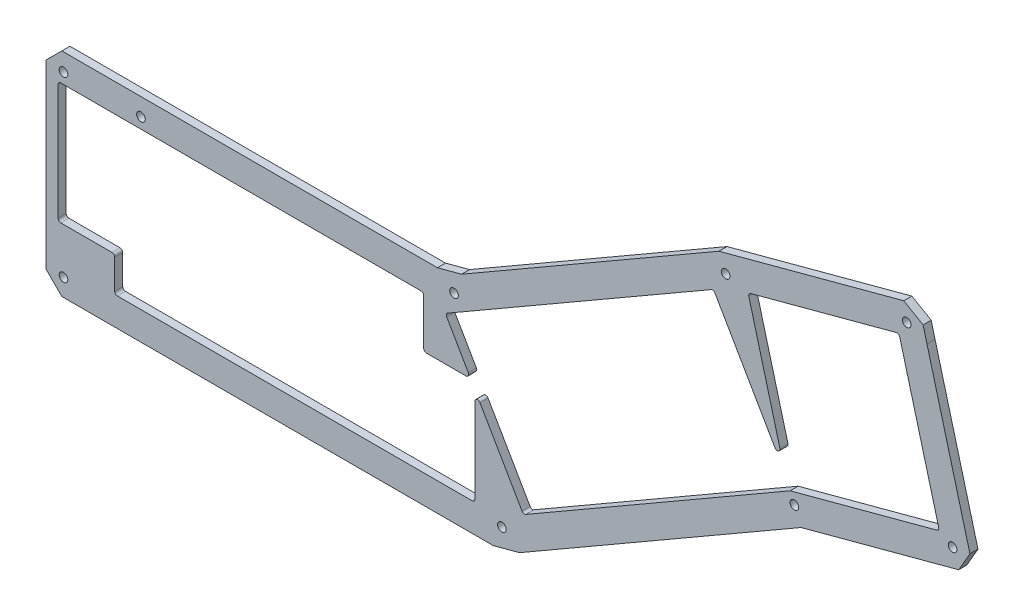
SolidWorks part; units mm, degrees
ref_plane "Plan de face" through (0, 0, 0) normal (0, 0, 1) x (1, 0, 0)
ref_plane "Plan de dessus" through (0, 0, 0) normal (0, 1, 0) x (1, 0, 0)
ref_plane "Plan de droite" through (0, 0, 0) normal (1, 0, 0) x (0, 0, -1)
sketch "Esquisse1" plane through (0, 0, 0) normal (0, 0, 1) x (1, 0, 0)
  line L0 (-73.9886, 18.0851) -> (-59.9886, 18.0851) construction
  line L1 (-73.9886, 37.0851) -> (-59.9886, 37.0851) construction
  line L2 (-73.9886, 37.0851) -> (-73.9886, 23.0851) construction
  line L3 (-73.9886, 23.0851) -> (-59.9886, 23.0851) construction
  line L4 (-59.9886, 37.0851) -> (-59.9886, 23.0851) construction
  line L5 (-73.9886, 18.0851) -> (-73.9886, 4.0851) construction
  line L6 (-73.9886, 4.0851) -> (-59.9886, 4.0851) construction
  line L7 (-59.9886, 18.0851) -> (-59.9886, 4.0851) construction
  line L8 (-73.9886, -0.9149) -> (-59.9886, -0.9149) construction
  line L9 (-73.9886, -0.9149) -> (-73.9886, -14.9149) construction
  line L10 (-73.9886, -14.9149) -> (-59.9886, -14.9149) construction
  line L11 (-59.9886, -0.9149) -> (-59.9886, -14.9149) construction
  line L12 (-73.9886, 37.0851) -> (-73.9886, 18.0851) construction
  line L13 (-54.9886, 18.0851) -> (-40.9886, 18.0851) construction
  line L14 (-54.9886, 37.0851) -> (-40.9886, 37.0851) construction
  line L15 (-54.9886, 37.0851) -> (-54.9886, 23.0851) construction
  line L16 (-54.9886, 23.0851) -> (-40.9886, 23.0851) construction
  line L17 (-40.9886, 37.0851) -> (-40.9886, 23.0851) construction
  line L18 (-54.9886, 18.0851) -> (-54.9886, 4.0851) construction
  line L19 (-54.9886, 4.0851) -> (-40.9886, 4.0851) construction
  line L20 (-40.9886, 18.0851) -> (-40.9886, 4.0851) construction
  line L21 (-54.9886, -0.9149) -> (-40.9886, -0.9149) construction
  line L22 (-54.9886, -0.9149) -> (-54.9886, -14.9149) construction
  line L23 (-54.9886, -14.9149) -> (-40.9886, -14.9149) construction
  line L24 (-40.9886, -0.9149) -> (-40.9886, -14.9149) construction
  line L25 (-54.9886, 37.0851) -> (-54.9886, 18.0851) construction
  line L26 (-35.9886, 18.0851) -> (-21.9886, 18.0851) construction
  line L27 (-35.9886, 37.0851) -> (-21.9886, 37.0851) construction
  line L28 (-35.9886, 37.0851) -> (-35.9886, 23.0851) construction
  line L29 (-35.9886, 23.0851) -> (-21.9886, 23.0851) construction
  line L30 (-21.9886, 37.0851) -> (-21.9886, 23.0851) construction
  line L31 (-35.9886, 18.0851) -> (-35.9886, 4.0851) construction
  line L32 (-35.9886, 4.0851) -> (-21.9886, 4.0851) construction
  line L33 (-21.9886, 18.0851) -> (-21.9886, 4.0851) construction
  line L34 (-35.9886, -0.9149) -> (-21.9886, -0.9149) construction
  line L35 (-35.9886, -0.9149) -> (-35.9886, -14.9149) construction
  line L36 (-35.9886, -14.9149) -> (-21.9886, -14.9149) construction
  line L37 (-21.9886, -0.9149) -> (-21.9886, -14.9149) construction
  line L38 (-35.9886, 37.0851) -> (-35.9886, 18.0851) construction
  line L39 (-16.9886, 18.0851) -> (-2.9886, 18.0851) construction
  line L40 (-16.9886, 37.0851) -> (-2.9886, 37.0851) construction
  line L41 (-16.9886, 37.0851) -> (-16.9886, 23.0851) construction
  line L42 (-16.9886, 23.0851) -> (-2.9886, 23.0851) construction
  line L43 (-2.9886, 37.0851) -> (-2.9886, 23.0851) construction
  line L44 (-16.9886, 18.0851) -> (-16.9886, 4.0851) construction
  line L45 (-16.9886, 4.0851) -> (-2.9886, 4.0851) construction
  line L46 (-2.9886, 18.0851) -> (-2.9886, 4.0851) construction
  line L47 (-16.9886, -0.9149) -> (-2.9886, -0.9149) construction
  line L48 (-16.9886, -0.9149) -> (-16.9886, -14.9149) construction
  line L49 (-16.9886, -14.9149) -> (-2.9886, -14.9149) construction
  line L50 (-2.9886, -0.9149) -> (-2.9886, -14.9149) construction
  line L51 (-16.9886, 37.0851) -> (-16.9886, 18.0851) construction
  line L52 (2.0114, 18.0851) -> (16.0114, 18.0851) construction
  line L53 (2.0114, 37.0851) -> (16.0114, 37.0851) construction
  line L54 (2.0114, 37.0851) -> (2.0114, 23.0851) construction
  line L55 (2.0114, 23.0851) -> (16.0114, 23.0851) construction
  line L56 (16.0114, 37.0851) -> (16.0114, 23.0851) construction
  line L57 (2.0114, 18.0851) -> (2.0114, 4.0851) construction
  line L58 (2.0114, 4.0851) -> (16.0114, 4.0851) construction
  line L59 (16.0114, 18.0851) -> (16.0114, 4.0851) construction
  line L60 (2.0114, -0.9149) -> (16.0114, -0.9149) construction
  line L61 (2.0114, -0.9149) -> (2.0114, -14.9149) construction
  line L62 (2.0114, -14.9149) -> (16.0114, -14.9149) construction
  line L63 (16.0114, -0.9149) -> (16.0114, -14.9149) construction
  line L64 (2.0114, 37.0851) -> (2.0114, 18.0851) construction
  line L65 (21.0114, 18.0851) -> (35.0114, 18.0851) construction
  line L66 (21.0114, 37.0851) -> (35.0114, 37.0851) construction
  line L67 (21.0114, 37.0851) -> (21.0114, 23.0851) construction
  line L68 (21.0114, 23.0851) -> (35.0114, 23.0851) construction
  line L69 (35.0114, 37.0851) -> (35.0114, 23.0851) construction
  line L70 (21.0114, 18.0851) -> (21.0114, 4.0851) construction
  line L71 (21.0114, 4.0851) -> (35.0114, 4.0851) construction
  line L72 (35.0114, 18.0851) -> (35.0114, 4.0851) construction
  line L73 (21.0114, -0.9149) -> (35.0114, -0.9149) construction
  line L74 (21.0114, -0.9149) -> (21.0114, -14.9149) construction
  line L75 (21.0114, -14.9149) -> (35.0114, -14.9149) construction
  line L76 (35.0114, -0.9149) -> (35.0114, -14.9149) construction
  line L77 (21.0114, 37.0851) -> (21.0114, 18.0851) construction
  line L78 (40.0114, 18.0851) -> (54.0114, 18.0851) construction
  line L79 (-97.7538, 39.0851) -> (-97.7538, 2.0851)
  line L80 (-97.7538, 39.0851) -> (-97.7538, 1.0851) construction
  line L81 (-76.7538, 0.0851) -> (-76.7538, -16.9149) construction
  line L82 (-95.7538, 44.0851) -> (-53.0442, 44.0851) construction
  line L83 (40.0114, 18.0851) -> (40.0114, 4.0851) construction
  line L84 (40.0114, 4.0851) -> (54.0114, 4.0851) construction
  line L85 (54.0114, 18.0851) -> (54.0114, 4.0851) construction
  line L86 (40.0114, -0.9149) -> (54.0114, -0.9149) construction
  line L87 (40.0114, -0.9149) -> (40.0114, -14.9149) construction
  line L88 (40.0114, -14.9149) -> (54.0114, -14.9149) construction
  line L89 (54.0114, -0.9149) -> (54.0114, -14.9149) construction
  line L90 (40.0114, 20.0851) -> (40.0114, 18.0851) construction
  line L91 (-73.9886, 18.0851) -> (-54.9886, 18.0851) construction
  line L92 (56.0114, 20.0851) -> (56.7532, 18.8002) construction
  line L93 (-66.9886, 37.0851) -> (-66.9886, 44.0851) construction
  line L94 (67.3933, 2.371) -> (74.3933, -9.7534) construction
  line L95 (146.1202, 94.012) -> (168.4398, 55.3534)
  line L96 (158.7183, 99.2303) -> (170.2717, 56.1122)
  line L97 (19.0114, 39.0851) -> (37.0114, 39.0851) construction
  line L98 (37.0114, 39.0851) -> (37.0114, 21.0851) construction
  line L99 (19.0114, 21.0851) -> (37.0114, 21.0851) construction
  line L100 (19.0114, 39.0851) -> (19.0114, 21.0851) construction
  line L101 (79.4363, 55.512) -> (88.4363, 39.9235) construction
  line L102 (88.4363, 39.9235) -> (72.8478, 30.9235) construction
  line L103 (63.8478, 46.512) -> (72.8478, 30.9235) construction
  line L104 (79.4363, 55.512) -> (63.8478, 46.512) construction
  line L105 (62.9818, 46.012) -> (71.9818, 30.4235) construction
  line L106 (71.9818, 30.4235) -> (56.3933, 21.4235) construction
  line L107 (47.3933, 37.012) -> (56.3933, 21.4235) construction
  line L108 (62.9818, 46.012) -> (47.3933, 37.012) construction
  line L109 (164.2542, 60.603) -> (148.6657, 51.603) construction
  line L110 (62.2497, 43.2799) -> (71.7497, 26.8254) construction
  line L111 (78.7042, 52.7799) -> (88.2042, 36.3254) construction
  line L112 (95.1587, 62.2799) -> (104.6587, 45.8254) construction
  line L113 (111.6132, 71.7799) -> (121.1132, 55.3254) construction
  line L114 (128.0677, 81.2799) -> (137.5677, 64.8254) construction
  line L115 (144.5221, 90.7799) -> (154.0221, 74.3254) construction
  line L116 (148.6657, 51.603) -> (157.6657, 36.0146) construction
  line L117 (69.1254, 3.371) -> (76.1254, -8.7534) construction
  line L118 (88.2497, -1.7534) -> (76.1254, -8.7534) construction
  line L119 (81.2497, 10.371) -> (88.2497, -1.7534) construction
  line L120 (81.2497, 10.371) -> (69.1254, 3.371) construction
  line L121 (59.6254, 19.8254) -> (66.6254, 7.7011) construction
  line L122 (78.7497, 14.7011) -> (66.6254, 7.7011) construction
  line L123 (71.7497, 26.8254) -> (78.7497, 14.7011) construction
  line L124 (50.1254, 36.2799) -> (57.1254, 24.1556) construction
  line L125 (69.2497, 31.1556) -> (57.1254, 24.1556) construction
  line L126 (62.2497, 43.2799) -> (69.2497, 31.1556) construction
  line L127 (62.2497, 43.2799) -> (50.1254, 36.2799) construction
  line L128 (71.7497, 26.8254) -> (59.6254, 19.8254) construction
  line L129 (85.5799, 12.871) -> (92.5799, 0.7466) construction
  line L130 (104.7042, 7.7466) -> (92.5799, 0.7466) construction
  line L131 (97.7042, 19.871) -> (104.7042, 7.7466) construction
  line L132 (97.7042, 19.871) -> (85.5799, 12.871) construction
  line L133 (76.0799, 29.3254) -> (83.0799, 17.2011) construction
  line L134 (95.2042, 24.2011) -> (83.0799, 17.2011) construction
  line L135 (88.2042, 36.3254) -> (95.2042, 24.2011) construction
  line L136 (66.5799, 45.7799) -> (73.5799, 33.6556) construction
  line L137 (85.7042, 40.6556) -> (73.5799, 33.6556) construction
  line L138 (78.7042, 52.7799) -> (85.7042, 40.6556) construction
  line L139 (78.7042, 52.7799) -> (66.5799, 45.7799) construction
  line L140 (88.2042, 36.3254) -> (76.0799, 29.3254) construction
  line L141 (102.0343, 22.371) -> (109.0343, 10.2466) construction
  line L142 (121.1587, 17.2466) -> (109.0343, 10.2466) construction
  line L143 (114.1587, 29.371) -> (121.1587, 17.2466) construction
  line L144 (114.1587, 29.371) -> (102.0343, 22.371) construction
  line L145 (92.5343, 38.8254) -> (99.5343, 26.7011) construction
  line L146 (111.6587, 33.7011) -> (99.5343, 26.7011) construction
  line L147 (104.6587, 45.8254) -> (111.6587, 33.7011) construction
  line L148 (83.0343, 55.2799) -> (90.0343, 43.1556) construction
  line L149 (102.1587, 50.1556) -> (90.0343, 43.1556) construction
  line L150 (95.1587, 62.2799) -> (102.1587, 50.1556) construction
  line L151 (95.1587, 62.2799) -> (83.0343, 55.2799) construction
  line L152 (104.6587, 45.8254) -> (92.5343, 38.8254) construction
  line L153 (118.4888, 31.871) -> (125.4888, 19.7466) construction
  line L154 (137.6132, 26.7466) -> (125.4888, 19.7466) construction
  line L155 (130.6132, 38.871) -> (137.6132, 26.7466) construction
  line L156 (130.6132, 38.871) -> (118.4888, 31.871) construction
  line L157 (108.9888, 48.3254) -> (115.9888, 36.2011) construction
  line L158 (128.1132, 43.2011) -> (115.9888, 36.2011) construction
  line L159 (121.1132, 55.3254) -> (128.1132, 43.2011) construction
  line L160 (99.4888, 64.7799) -> (106.4888, 52.6556) construction
  line L161 (118.6132, 59.6556) -> (106.4888, 52.6556) construction
  line L162 (111.6132, 71.7799) -> (118.6132, 59.6556) construction
  line L163 (111.6132, 71.7799) -> (99.4888, 64.7799) construction
  line L164 (121.1132, 55.3254) -> (108.9888, 48.3254) construction
  line L165 (134.9433, 41.371) -> (141.9433, 29.2466) construction
  line L166 (154.0677, 36.2466) -> (141.9433, 29.2466) construction
  line L167 (147.0677, 48.371) -> (154.0677, 36.2466) construction
  line L168 (147.0677, 48.371) -> (134.9433, 41.371) construction
  line L169 (125.4433, 57.8254) -> (132.4433, 45.7011) construction
  line L170 (144.5677, 52.7011) -> (132.4433, 45.7011) construction
  line L171 (137.5677, 64.8254) -> (144.5677, 52.7011) construction
  line L172 (115.9433, 74.2799) -> (122.9433, 62.1556) construction
  line L173 (135.0677, 69.1556) -> (122.9433, 62.1556) construction
  line L174 (128.0677, 81.2799) -> (135.0677, 69.1556) construction
  line L175 (128.0677, 81.2799) -> (115.9433, 74.2799) construction
  line L176 (137.5677, 64.8254) -> (125.4433, 57.8254) construction
  line L177 (151.3978, 50.871) -> (158.3978, 38.7466) construction
  line L178 (170.5221, 45.7466) -> (158.3978, 38.7466) construction
  line L179 (163.5221, 57.871) -> (170.5221, 45.7466) construction
  line L180 (163.5221, 57.871) -> (151.3978, 50.871) construction
  line L181 (141.8978, 67.3254) -> (148.8978, 55.2011) construction
  line L182 (161.0221, 62.2011) -> (148.8978, 55.2011) construction
  line L183 (154.0221, 74.3254) -> (161.0221, 62.2011) construction
  line L184 (132.3978, 83.7799) -> (139.3978, 71.6556) construction
  line L185 (151.5221, 78.6556) -> (139.3978, 71.6556) construction
  line L186 (144.5221, 90.7799) -> (151.5221, 78.6556) construction
  line L187 (144.5221, 90.7799) -> (132.3978, 83.7799) construction
  line L188 (154.0221, 74.3254) -> (141.8978, 67.3254) construction
  line L189 (173.2542, 45.0146) -> (157.6657, 36.0146) construction
  line L190 (164.2542, 60.603) -> (173.2542, 45.0146) construction
  line L191 (178.3169, 34.0986) -> (169.0534, 56.4627) construction
  line L192 (169.5193, 62.7839) -> (174.1781, 45.3972) construction
  line L193 (174.1781, 45.3972) -> (191.5647, 50.056) construction
  line L194 (186.906, 67.4426) -> (191.5647, 50.056) construction
  line L195 (162.1337, 98.0749) -> (167.0513, 79.7223) construction
  line L196 (169.5193, 62.7839) -> (186.906, 67.4426) construction
  line L197 (167.0513, 79.7223) -> (180.5742, 83.3457) construction
  line L198 (162.1337, 98.0749) -> (175.6567, 101.6983) construction
  line L199 (162.1337, 98.0749) -> (165.7572, 84.5519) construction
  line L200 (165.7572, 84.5519) -> (179.2801, 88.1754) construction
  line L201 (175.6567, 101.6983) -> (179.2801, 88.1754) construction
  line L202 (167.0513, 79.7223) -> (170.6747, 66.1993) construction
  line L203 (170.6747, 66.1993) -> (184.1977, 69.8228) construction
  line L204 (180.5742, 83.3457) -> (184.1977, 69.8228) construction
  line L205 (171.9688, 61.3697) -> (185.4918, 64.9932) construction
  line L206 (171.9688, 61.3697) -> (175.5923, 47.8467) construction
  line L207 (175.5923, 47.8467) -> (189.1152, 51.4702) construction
  line L208 (185.4918, 64.9932) -> (189.1152, 51.4702) construction
  line L209 (185.4038, 84.6398) -> (198.9268, 88.2633) construction
  line L210 (180.4863, 102.9924) -> (194.0092, 106.6159) construction
  line L211 (180.4863, 102.9924) -> (184.1097, 89.4695) construction
  line L212 (184.1097, 89.4695) -> (197.6327, 93.0929) construction
  line L213 (194.0092, 106.6159) -> (197.6327, 93.0929) construction
  line L214 (185.4038, 84.6398) -> (189.0273, 71.1169) construction
  line L215 (189.0273, 71.1169) -> (202.5503, 74.7403) construction
  line L216 (198.9268, 88.2633) -> (202.5503, 74.7403) construction
  line L217 (190.3214, 66.2873) -> (203.8444, 69.9107) construction
  line L218 (190.3214, 66.2873) -> (193.9449, 52.7643) construction
  line L219 (193.9449, 52.7643) -> (207.4678, 56.3878) construction
  line L220 (203.8444, 69.9107) -> (207.4678, 56.3878) construction
  line L221 (187.8719, 67.7015) -> (192.5307, 50.3148) construction
  line L222 (192.5307, 50.3148) -> (209.9173, 54.9735) construction
  line L223 (205.2586, 72.3602) -> (209.9173, 54.9735) construction
  line L224 (180.4863, 102.9924) -> (185.4038, 84.6398) construction
  line L225 (187.8719, 67.7015) -> (205.2586, 72.3602) construction
  line L226 (203.7564, 89.5574) -> (217.2794, 93.1809) construction
  line L227 (198.8389, 107.91) -> (212.3618, 111.5335) construction
  line L228 (198.8389, 107.91) -> (202.4623, 94.387) construction
  line L229 (202.4623, 94.387) -> (215.9853, 98.0105) construction
  line L230 (212.3618, 111.5335) -> (215.9853, 98.0105) construction
  line L231 (203.7564, 89.5574) -> (207.3799, 76.0344) construction
  line L232 (207.3799, 76.0344) -> (220.9029, 79.6579) construction
  line L233 (217.2794, 93.1809) -> (220.9029, 79.6579) construction
  line L234 (208.674, 71.2048) -> (222.197, 74.8283) construction
  line L235 (208.674, 71.2048) -> (212.2975, 57.6819) construction
  line L236 (212.2975, 57.6819) -> (225.8204, 61.3053) construction
  line L237 (222.197, 74.8283) -> (225.8204, 61.3053) construction
  line L238 (206.2245, 72.619) -> (210.8833, 55.2324) construction
  line L239 (210.8833, 55.2324) -> (228.2699, 59.8911) construction
  line L240 (223.6112, 77.2778) -> (228.2699, 59.8911) construction
  line L241 (198.8389, 107.91) -> (203.7564, 89.5574) construction
  line L242 (206.2245, 72.619) -> (223.6112, 77.2778) construction
  line L243 (167.0513, 79.7223) -> (185.4038, 84.6398) construction
  line L244 (38.0114, 20.0851) -> (56.0114, 20.0851) construction
  line L245 (56.0114, 20.0851) -> (56.0114, 2.0851) construction
  line L246 (38.0114, 2.0851) -> (56.0114, 2.0851) construction
  line L247 (38.0114, 20.0851) -> (38.0114, 2.0851) construction
  line L248 (72.4818, 29.5575) -> (56.8933, 20.5575) construction
  line L249 (56.8933, 20.5575) -> (65.8933, 4.969) construction
  line L250 (81.4818, 13.969) -> (65.8933, 4.969) construction
  line L251 (72.4818, 29.5575) -> (81.4818, 13.969) construction
  line L252 (56.8933, 20.5575) -> (57.6111, 19.3142) construction
  line L253 (164.6018, 81.1365) -> (169.2605, 63.7498) construction
  line L254 (169.2605, 63.7498) -> (186.6472, 68.4086) construction
  line L255 (181.9884, 85.7952) -> (186.6472, 68.4086) construction
  line L256 (164.6018, 81.1365) -> (181.9884, 85.7952) construction
  line L257 (154.7542, 77.0575) -> (163.7542, 61.469) construction
  line L258 (163.7542, 61.469) -> (148.1657, 52.469) construction
  line L259 (139.1657, 68.0575) -> (148.1657, 52.469) construction
  line L260 (154.7542, 77.0575) -> (139.1657, 68.0575) construction
  line L261 (196.3894, 109.3242) -> (213.776, 113.983) construction
  line L262 (-94.7538, 35.7952) -> (-76.7538, 35.7952) construction
  line L263 (-94.7538, 35.7952) -> (-94.7538, 2.7952) construction
  line L264 (-94.7538, 2.7952) -> (-76.7538, 2.7952) construction
  line L265 (-76.7538, 35.7952) -> (-76.7538, 2.7952) construction
  line L266 (213.776, 113.983) -> (218.4348, 96.5963) construction
  line L267 (201.0481, 91.9375) -> (218.4348, 96.5963) construction
  line L268 (196.3894, 109.3242) -> (201.0481, 91.9375) construction
  line L269 (-75.9886, -16.9149) -> (-57.9886, -16.9149) construction
  line L270 (-57.9886, 1.0851) -> (-57.9886, -16.9149) construction
  line L271 (-75.9886, 1.0851) -> (-57.9886, 1.0851) construction
  line L272 (-75.9886, 1.0851) -> (-75.9886, -16.9149) construction
  line L273 (38.0114, -16.9149) -> (56.0114, -16.9149) construction
  line L274 (56.0114, 1.0851) -> (56.0114, -16.9149) construction
  line L275 (38.0114, 1.0851) -> (56.0114, 1.0851) construction
  line L276 (38.0114, 1.0851) -> (38.0114, -16.9149) construction
  line L277 (-75.9886, 39.0851) -> (-57.9886, 39.0851) construction
  line L278 (-57.9886, 39.0851) -> (-57.9886, 21.0851) construction
  line L279 (-75.9886, 21.0851) -> (-57.9886, 21.0851) construction
  line L280 (-75.9886, 39.0851) -> (-75.9886, 21.0851) construction
  line L281 (145.2542, 93.512) -> (129.6657, 84.512) construction
  line L282 (129.6657, 84.512) -> (138.6657, 68.9235) construction
  line L283 (154.2542, 77.9235) -> (138.6657, 68.9235) construction
  line L284 (145.2542, 93.512) -> (154.2542, 77.9235) construction
  line L285 (223.4353, 116.5711) -> (228.0941, 99.1845) construction
  line L286 (148.2159, 106.7689) -> (211.1879, 123.6422) construction
  line L287 (177.5508, 35.9482) -> (235.6877, 51.5259) construction
  line L288 (177.5508, 35.9482) -> (72.9989, -24.4149) construction
  line L289 (-95.7538, -26.9149) -> (63.6687, -26.9149) construction
  line L290 (-100.7538, 35.7952) -> (-100.7538, -21.9149) construction
  line L291 (-75.9886, 49.0851) -> (43.3046, 49.0851) construction
  line L292 (148.2159, 106.7689) -> (52.6347, 51.5851) construction
  line L293 (-75.9886, 49.0851) -> (-57.9886, 49.0851) construction
  line L294 (140.2542, 102.1722) -> (124.6657, 93.1722) construction
  line L295 (193.8012, 118.9835) -> (211.1879, 123.6422) construction
  line L296 (213.4714, 45.5731) -> (230.8581, 50.2318) construction
  line L297 (38.0114, -26.9149) -> (38.0114, -85.4624) construction
  line L298 (178.2542, 36.3543) -> (162.6657, 27.3543) construction
  line L299 (38.0114, -26.9149) -> (56.0114, -26.9149) construction
  line L300 (-100.7538, 2.7952) -> (-100.7538, -38.0419) construction
  line L301 (-100.7538, 35.7952) -> (-100.7538, 2.7952) construction
  line L302 (-75.9886, 49.0851) -> (-95.7538, 49.0851) construction
  line L303 (-100.7538, 44.0851) -> (-100.7538, 35.7952) construction
  line L304 (211.1879, 123.6422) -> (216.0732, 124.9512) construction
  line L305 (222.1691, 121.4083) -> (223.4353, 116.5711) construction
  line L306 (228.0941, 99.1845) -> (239.2233, 57.6497) construction
  line L307 (216.0732, 124.9512) -> (222.1691, 121.4083) construction
  line L308 (235.6877, 51.5259) -> (239.2233, 57.6497) construction
  line L309 (63.6687, -26.9149) -> (72.9989, -24.4149) construction
  line L310 (52.6347, 51.5851) -> (43.3046, 49.0851) construction
  line L311 (-95.7538, 49.0851) -> (-100.7538, 44.0851) construction
  line L312 (-100.7538, -21.9149) -> (-95.7538, -26.9149) construction
  line L313 (-95.7538, 49.0851) -> (-95.7538, 44.0851) construction
  line L314 (-95.7538, 44.0851) -> (-100.7538, 44.0851) construction
  line L315 (-95.7538, -26.9149) -> (-95.7538, -21.9149) construction
  line L316 (68.3338, -25.6649) -> (67.0397, -20.8353) construction
  line L317 (47.9697, 50.3351) -> (49.2637, 45.5055) construction
  line L318 (177.5508, 35.9482) -> (175.6374, 40.5676) construction
  line L319 (148.2159, 106.7689) -> (150.1293, 102.1495) construction
  line L320 (239.2233, 57.6497) -> (234.3936, 56.3556) construction
  line L321 (216.0732, 124.9512) -> (217.3634, 120.1206) construction
  line L322 (146.1202, 94.012) -> (155.1202, 78.4235) construction
  line L323 (-76.7538, 35.7952) -> (-96.7538, 35.7952) construction
  line L324 (148.6019, 105.8371) -> (53.0207, 50.6533) construction
  line L325 (163.6358, 80.8777) -> (168.2946, 63.491) construction
  line L326 (57.0114, 14.621) -> (57.0114, -16.9149)
  line L327 (-77.7538, 1.0851) -> (-96.7538, 1.0851) construction
  line L328 (-96.7538, 39.0851) -> (-96.7538, 1.0851) construction
  line L329 (53.0207, 50.6533) -> (43.4362, 48.0851) construction
  line L330 (-75.9886, 48.0851) -> (43.4362, 48.0851) construction
  line L331 (-75.9886, 48.0851) -> (-95.3395, 48.0851) construction
  line L332 (-95.3395, 48.0851) -> (-99.7538, 43.6709) construction
  line L333 (-99.7538, 43.6709) -> (-99.7538, 35.7952) construction
  line L334 (-99.7538, 35.7952) -> (-99.7538, -21.5007) construction
  line L335 (-99.7538, -21.5007) -> (-95.3395, -25.9149) construction
  line L336 (-95.3395, -25.9149) -> (63.5371, -25.9149) construction
  line L337 (63.5371, -25.9149) -> (72.6129, -23.483) construction
  line L338 (177.1648, 36.88) -> (72.6129, -23.483) construction
  line L339 (177.1648, 36.88) -> (235.0288, 52.3847) construction
  line L340 (235.0288, 52.3847) -> (238.1501, 57.7909) construction
  line L341 (227.1281, 98.9257) -> (238.1501, 57.7909) construction
  line L342 (222.4686, 116.3151) -> (227.1281, 98.9257) construction
  line L343 (221.307, 120.7527) -> (222.4686, 116.3151) construction
  line L344 (215.9303, 123.8777) -> (221.307, 120.7527) construction
  line L345 (211.4467, 122.6763) -> (215.9303, 123.8777) construction
  line L346 (148.6019, 105.8371) -> (211.4467, 122.6763) construction
  line L347 (214.742, 114.2418) -> (229.2358, 60.1499)
  line L348 (174.0769, 44.3349) -> (228.5287, 58.9252)
  line L349 (174.0769, 44.3349) -> (75.8933, -12.3515)
  line L350 (159.4254, 100.455) -> (213.5172, 114.9489)
  line L351 (144.7542, 94.378) -> (46.8933, 37.878)
  line L352 (-75.7538, -17.9149) -> (56.0114, -17.9149)
  line L353 (-96.7538, 40.0851) -> (37.0114, 40.0851)
  line L354 (2.0114, 40.0851) -> (16.0114, 40.0851) construction
  line L355 (126.5677, 83.878) -> (114.4433, 76.878) construction
  line L356 (179.7098, 105.8902) -> (193.2328, 109.5137) construction
  line L357 (215.2596, 112.3099) -> (218.8831, 98.787) construction
  line L358 (194.7213, 49.8665) -> (208.2443, 53.49) construction
  line L359 (155.5677, 33.6485) -> (143.4433, 26.6485) construction
  line L360 (40.0114, -17.9149) -> (54.0114, -17.9149) construction
  line L361 (58.8774, 15.121) -> (74.5273, -11.9854)
  line L362 (66.5273, 1.871) -> (73.5273, -10.2534) construction
  line L363 (40.0114, 37.0851) -> (40.0114, 23.0851) construction
  line L364 (57.0114, 1.0851) -> (57.0114, -16.9149) construction
  line L365 (46.5273, 36.512) -> (54.568, 22.5851)
  line L366 (51.52, 37.0851) -> (54.0114, 37.0851) construction
  line L367 (40.0114, 23.0851) -> (54.0114, 23.0851) construction
  line L368 (39.0114, 21.0851) -> (53.702, 21.0851)
  line L369 (54.0114, 29.5492) -> (54.0114, 25.5492) construction
  line L370 (38.0114, 39.0851) -> (38.0114, 22.0851)
  line L371 (38.0114, 39.0851) -> (38.0114, 21.0851) construction
  line L372 (46.5273, 36.512) -> (55.5273, 20.9235) construction
  line L373 (-75.9886, 48.5851) -> (43.3704, 48.5851) construction
  line L374 (38.0114, 21.0851) -> (56.0114, 21.0851) construction
  line L375 (52.8277, 51.1192) -> (43.3704, 48.5851) construction
  line L376 (148.4089, 106.303) -> (52.8277, 51.1192) construction
  line L377 (148.4089, 106.303) -> (211.3173, 123.1592) construction
  line L378 (211.3173, 123.1592) -> (216.0018, 124.4145) construction
  line L379 (216.0018, 124.4145) -> (221.738, 121.0805) construction
  line L380 (221.738, 121.0805) -> (222.952, 116.4431) construction
  line L381 (222.952, 116.4431) -> (227.6111, 99.0551) construction
  line L382 (227.6111, 99.0551) -> (238.6867, 57.7203) construction
  line L383 (235.3583, 51.9553) -> (238.6867, 57.7203) construction
  line L384 (177.3578, 36.4141) -> (235.3583, 51.9553) construction
  line L385 (177.3578, 36.4141) -> (72.8059, -23.949) construction
  line L386 (63.6029, -26.4149) -> (72.8059, -23.949) construction
  line L387 (-95.5467, -26.4149) -> (63.6029, -26.4149) construction
  line L388 (-100.2538, -21.7078) -> (-95.5467, -26.4149) construction
  line L389 (-100.2538, 35.7952) -> (-100.2538, -21.7078) construction
  line L390 (-100.2538, 43.878) -> (-100.2538, 35.7952) construction
  line L391 (-95.5467, 48.5851) -> (-100.2538, 43.878) construction
  line L392 (-75.9886, 48.5851) -> (-95.5467, 48.5851) construction
  line L393 (-75.9886, 49.5851) -> (43.2388, 49.5851) construction
  line L394 (52.4417, 52.051) -> (43.2388, 49.5851) construction
  line L395 (148.0229, 107.2348) -> (52.4417, 52.051) construction
  line L396 (148.0229, 107.2348) -> (211.0584, 124.1252) construction
  line L397 (211.0584, 124.1252) -> (216.1447, 125.488) construction
  line L398 (216.1447, 125.488) -> (222.6001, 121.7361) construction
  line L399 (222.6001, 121.7361) -> (223.9186, 116.6992) construction
  line L400 (223.9186, 116.6992) -> (228.577, 99.3139) construction
  line L401 (228.577, 99.3139) -> (239.7598, 57.579) construction
  line L402 (236.0172, 51.0966) -> (239.7598, 57.579) construction
  line L403 (177.7438, 35.4823) -> (236.0172, 51.0966) construction
  line L404 (177.7438, 35.4823) -> (73.1918, -24.8808) construction
  line L405 (63.7346, -27.4149) -> (73.1918, -24.8808) construction
  line L406 (-95.9609, -27.4149) -> (63.7346, -27.4149) construction
  line L407 (-101.2538, -22.122) -> (-95.9609, -27.4149) construction
  line L408 (-101.2538, 35.7952) -> (-101.2538, -22.122) construction
  line L409 (-101.2538, 44.2922) -> (-101.2538, 35.7952) construction
  line L410 (-95.9609, 49.5851) -> (-101.2538, 44.2922) construction
  line L411 (-75.9886, 49.5851) -> (-95.9609, 49.5851) construction
  line L412 (-75.9886, 50.5851) -> (-96.3751, 50.5851)
  line L413 (-96.3751, 50.5851) -> (-102.2538, 44.7064)
  line L414 (-102.2538, 44.7064) -> (-102.2538, 35.7952)
  line L415 (-102.2538, 35.7952) -> (-102.2538, -22.5362)
  line L416 (-102.2538, -22.5362) -> (-96.3751, -28.4149)
  line L417 (-96.3751, -28.4149) -> (63.8662, -28.4149)
  line L418 (63.8662, -28.4149) -> (73.5778, -25.8127)
  line L419 (178.1298, 34.5504) -> (73.5778, -25.8127)
  line L420 (178.1298, 34.5504) -> (236.6761, 50.2379)
  line L421 (236.6761, 50.2379) -> (240.833, 57.4377)
  line L422 (229.5429, 99.5727) -> (240.833, 57.4377)
  line L423 (224.8853, 116.9552) -> (229.5429, 99.5727)
  line L424 (223.4622, 122.3917) -> (224.8853, 116.9552)
  line L425 (216.2876, 126.5616) -> (223.4622, 122.3917)
  line L426 (210.7996, 125.0911) -> (216.2876, 126.5616)
  line L427 (147.6369, 108.1667) -> (210.7996, 125.0911)
  line L428 (147.6369, 108.1667) -> (52.0557, 52.9829)
  line L429 (52.0557, 52.9829) -> (43.1071, 50.5851)
  line L430 (-75.9886, 50.5851) -> (43.1071, 50.5851)
  line L431 (-77.7538, -4.9149) -> (-96.7538, -4.9149)
  line L432 (-77.7538, -4.9149) -> (-96.7538, -4.9149) construction
  line L433 (-97.7538, 2.0851) -> (-97.7538, -3.9149)
  line L434 (-76.7538, -5.9149) -> (-76.7538, -16.9149)
  circle A0 centre (-95.7538, 44.0851) radius 1.5 construction
  circle A1 centre (-95.7538, -21.9149) radius 1.5 construction
  circle A2 centre (67.0397, -20.8353) radius 1.5 construction
  circle A3 centre (49.2637, 45.5055) radius 1.5 construction
  circle A4 centre (175.6374, 40.5676) radius 1.5 construction
  circle A5 centre (150.1293, 102.1495) radius 1.5 construction
  circle A6 centre (234.3936, 56.3556) radius 1.5 construction
  circle A7 centre (217.3634, 120.1206) radius 1.5 construction
  circle A8 centre (-66.9886, 44.0851) radius 1.5 construction
  arc A9 (168.4398, 55.3534) -> (170.2717, 56.1122) centre (169.3058, 55.8534) ccw
  arc A10 (57.0114, 14.621) -> (58.8774, 15.121) centre (58.0114, 14.621) cw
  arc A11 (53.702, 21.0851) -> (54.568, 22.5851) centre (53.702, 22.0851) ccw
  arc A12 (39.0114, 21.0851) -> (38.0114, 22.0851) centre (39.0114, 22.0851) cw
  arc A13 (-97.7538, 39.0851) -> (-96.7538, 40.0851) centre (-96.7538, 39.0851) cw
  arc A14 (-96.7538, 1.0851) -> (-97.7538, 2.0851) centre (-96.7538, 2.0851) cw construction
  arc A15 (-76.7538, 0.0851) -> (-77.7538, 1.0851) centre (-77.7538, 0.0851) ccw construction
  arc A16 (-76.7538, -16.9149) -> (-75.7538, -17.9149) centre (-75.7538, -16.9149) ccw
  arc A17 (228.5287, 58.9252) -> (229.2358, 60.1499) centre (228.2699, 59.8911) ccw
  arc A18 (214.742, 114.2418) -> (213.5172, 114.9489) centre (213.776, 113.983) ccw
  arc A19 (158.7183, 99.2303) -> (159.4254, 100.455) centre (159.6842, 99.4891) cw
  arc A20 (146.1202, 94.012) -> (144.7542, 94.378) centre (145.2542, 93.512) ccw
  arc A21 (57.0114, -16.9149) -> (56.0114, -17.9149) centre (56.0114, -16.9149) cw
  arc A22 (74.5273, -11.9854) -> (75.8933, -12.3515) centre (75.3933, -11.4854) ccw
  arc A23 (46.5273, 36.512) -> (46.8933, 37.878) centre (47.3933, 37.012) cw
  arc A24 (38.0114, 39.0851) -> (37.0114, 40.0851) centre (37.0114, 39.0851) ccw
  circle A25 centre (-95.7538, 44.0851) radius 1.6
  circle A26 centre (-66.9886, 44.0851) radius 1.6
  circle A27 centre (-95.7538, -21.9149) radius 1.6
  circle A28 centre (49.2637, 45.5055) radius 1.6
  circle A29 centre (67.0397, -20.8353) radius 1.6
  circle A30 centre (175.6374, 40.5676) radius 1.6
  circle A31 centre (234.3936, 56.3556) radius 1.6
  circle A32 centre (217.3634, 120.1206) radius 1.6
  circle A33 centre (150.1293, 102.1495) radius 1.6
  arc A34 (-97.7538, -3.9149) -> (-96.7538, -4.9149) centre (-96.7538, -3.9149) ccw
  arc A35 (-77.7538, -4.9149) -> (-76.7538, -5.9149) centre (-77.7538, -5.9149) cw
  point P85 (40.0114, 37.0851)
  point P86 (54.0114, 23.0851)
  point P88 (54.0114, 37.0851)
  point P102 (38.0114, 39.0851)
  point P103 (56.0114, 39.0851)
  point P304 (48.3046, 49.0851)
  point P305 (240.5174, 52.82)
  point P308 (68.6687, -26.9149)
  point P309 (-100.7538, -26.9149)
  point P311 (-100.7538, 49.0851)
  point P312 (220.9029, 126.2453)
  point P409 (172.2377, 48.7752)
  point P537 (-76.7538, -4.9149)
  dimension "D32" = 3
  dimension "D33" = 5
  dimension "D40" = 5
  dimension "D41" = 5
  dimension "D42" = 5
  dimension "D43" = 5
  dimension "D44" = 20
  dimension "D53" = 2
  dimension "D56" = 1
  dimension "D59" = 1
  dimension "D63" = 1
  dimension "D64" = 1
  dimension "D65" = 1
  dimension "D71" = 1
  dimension "D1" = 14
  dimension "D2" = 14
  dimension "D4" = 19
  dimension "D6" = 19
  dimension "D7" = 30
  dimension "D10" = 1
  dimension "D11" = 2
  dimension "D13" = 0.5
  dimension "D15" = 2
  dimension "D12" = 7.5
  dimension "D14" = 19
  dimension "D18" = 2
  dimension "D20" = 18
  dimension "D21" = 33
  dimension "D22" = 2
  dimension "D8" = 1
  dimension "D9" = 2
  dimension "D16" = 2
  dimension "D19" = 2
  dimension "D23" = 2
  dimension "D24" = 10
  dimension "D25" = 10
  dimension "D26" = 10
  dimension "D27" = 10
  dimension "D28" = 10
  dimension "D29" = 6
  dimension "D30" = 10
  dimension "D31" = 10
  dimension "D45" = 1
  dimension "D46" = 3
  dimension "D47" = 3
  dimension "D48" = 3
  dimension "D49" = 3
  dimension "D50" = 3
  dimension "D51" = 3
  dimension "D52" = 3
  dimension "D54" = 1
  dimension "D55" = 1
  dimension "D57" = 1
  dimension "D58" = 1
  dimension "D60" = 1
  dimension "D61" = 1
  dimension "D62" = 1
  dimension "D66" = 0.5
  dimension "D67" = 1
  dimension "D68" = 1
  dimension "D69" = 0.1
  dimension "D70" = 6
  dimension "D3" = 3
  dimension "D5" = 7
  dimension "D17" = 3
extrude "Boss.-Extru.1" add sketch "Esquisse1" along normal blind 3
